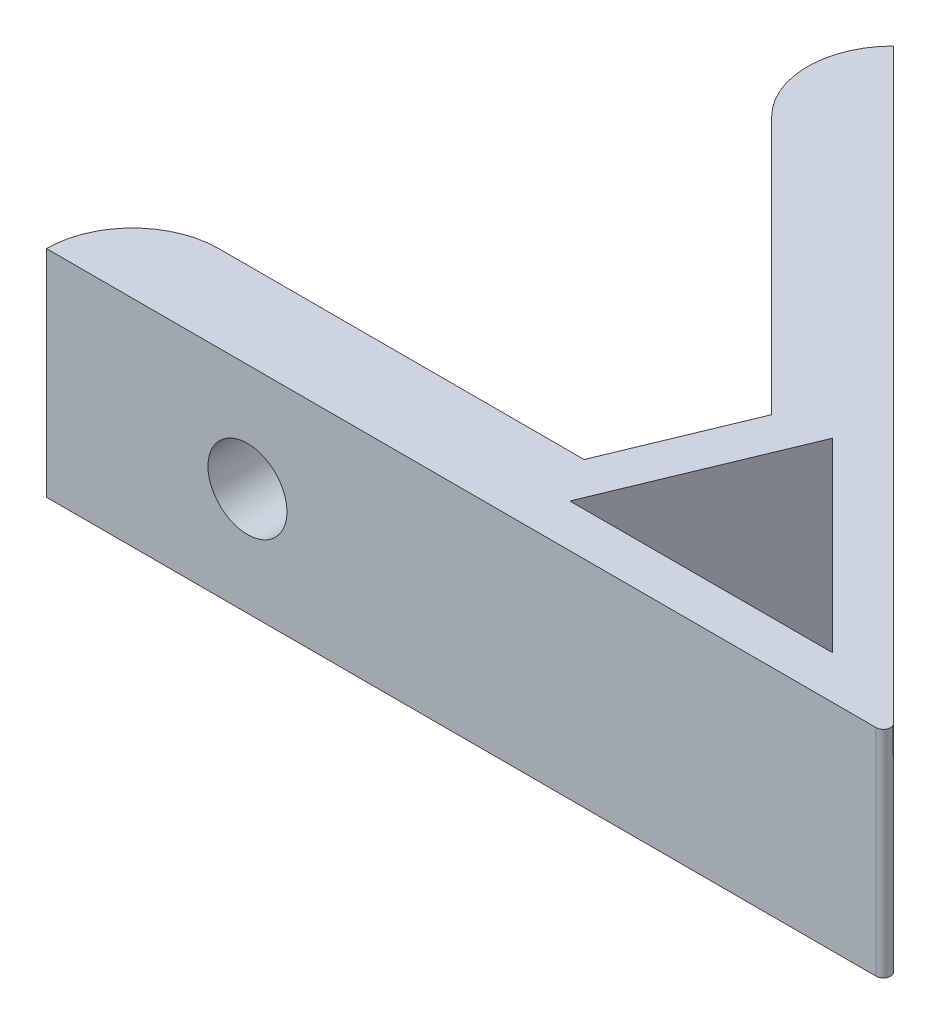
SolidWorks part; units mm, degrees
ref_plane "Front Plane" through (0, 0, 0) normal (0, 0, 1) x (1, 0, 0)
ref_plane "Top Plane" through (0, 0, 0) normal (0, 1, 0) x (1, 0, 0)
ref_plane "Right Plane" through (0, 0, 0) normal (1, 0, 0) x (0, 0, -1)
sketch "Sketch1" plane through (0, 0, 0) normal (0, 1, 0) x (1, 0, 0)
  line L0 (0, 0) -> (-59, 0)
  line L1 (-59, 0) -> (-59, 6)
  line L3 (0, 0) -> (-41.7193, 41.7193)
  line L4 (-41.7193, 41.7193) -> (-45.9619, 37.4767)
  line L5 (-45.9619, 37.4767) -> (-23.7241, 15.2388)
  line L6 (-23.7241, 15.2388) -> (-27.5509, 6)
  line L7 (-27.5509, 6) -> (-59, 6)
  dimension "D1" = 59
  dimension "D2" = 59
  dimension "D3" = 6
  dimension "D4" = 6
  dimension "D5" = 45
  dimension "D6" = 112.5
  dimension "D7" = 10
extrude "Boss-Extrude1" add sketch "Sketch1" along normal blind 15
fillet "Fillet1" radius 6 2 edges at (-45.9619, 7.5, -37.4767) (-59, 7.5, -6)
fillet "Fillet2" radius 0.5 1 edges at (0, 7.5, 0)
sketch "Sketch2" plane through (0, 15, 0) normal (0, 1, 0) x (1, 0, 0)
  line L0 (-20.1853, 15.9427) -> (-7.2426, 3)
  line L1 (-7.2426, 3) -> (-25.5464, 3)
  line L2 (-25.5464, 3) -> (-20.1853, 15.9427)
  line L5 (-0.8536, 0.8536) -> (-41.7193, 41.7193) construction
  line L6 (-59, 0) -> (-1.2071, 0) construction
  line L7 (-23.7241, 15.2388) -> (-27.5509, 6) construction
  dimension "D1" = 3
  dimension "D2" = 3
  dimension "D3" = 3
extrude "Cut-Extrude1" cut sketch "Sketch2" against normal through all
sketch "Sketch3" plane through (0, 0, -6) normal (0, 0, -1) x (-1, 0, 0)
  line L0 (53, 0) -> (53, 15) construction
  line L1 (27.5509, 15) -> (53, 15) construction
  circle A0 centre (45, 7.5) radius 2.75
  dimension "D1" = 5.5
  dimension "D2" = 8
  dimension "D3" = 7.5
extrude "Cut-Extrude2" cut sketch "Sketch3" against normal through all
sketch "Sketch4" plane through (-4.2426, 0, 4.2426) normal (-0.7071, 0, 0.7071) x (0.7071, 0, 0.7071)
  line L0 (-53, 15) -> (-53, 0) construction
  line L1 (-53, 15) -> (-27.5509, 15) construction
  circle A0 centre (-45, 7.5) radius 2.75
  dimension "D1" = 5.5
  dimension "D2" = 8
  dimension "D3" = 7.5
extrude "Cut-Extrude3" cut sketch "Sketch4" against normal through all
